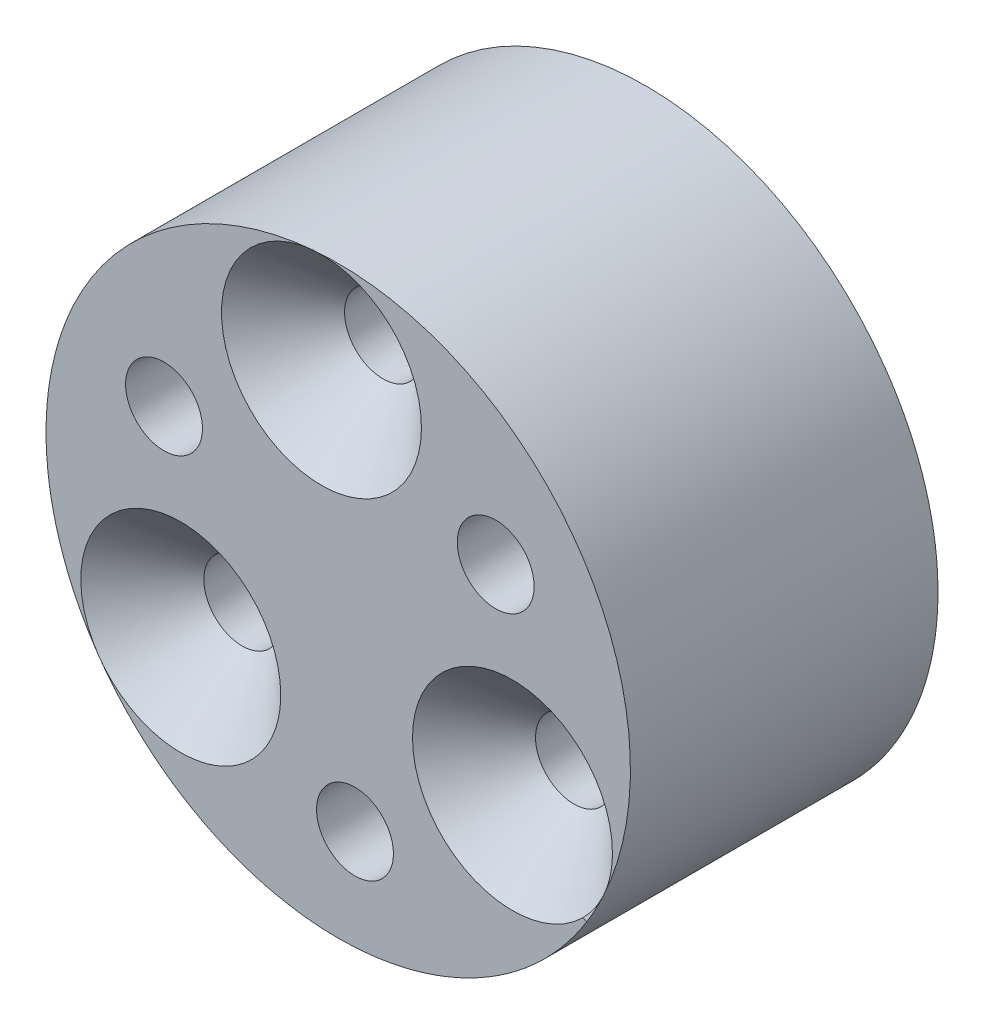
SolidWorks part; units mm, degrees
ref_plane "Top Plane" through (0, 0, 0) normal (0, 0, 1) x (1, 0, 0)
ref_plane "Right Plane" through (0, 0, 0) normal (0, 1, 0) x (1, 0, 0)
ref_plane "Front Plane" through (0, 0, 0) normal (1, 0, 0) x (0, 0, -1)
sketch "Sketch1" plane through (0, 0, 0) normal (0, 0, 1) x (1, 0, 0)
  line L0 (-0.5447, -33.7738) -> (0.5447, -46.2262) construction
  line L2 (5.1197, -36.4151) -> (-5.1197, -43.5849) construction
  line L4 (-5.6644, -37.3586) -> (5.6644, -42.6414) construction
  circle A0 centre (0, -40) radius 6.25 construction
  circle A1 centre (-0.5447, -33.7738) radius 1.25 construction
  circle A2 centre (0, -40) radius 9.5
  circle A3 centre (5.1197, -36.4151) radius 1.25
  circle A4 centre (0.5447, -46.2262) radius 1.25
  circle A5 centre (-5.6644, -37.3586) radius 1.25
  circle A6 centre (-5.1197, -43.5849) radius 1.25 construction
  circle A8 centre (-5.1197, -43.5849) radius 1.25
  circle A9 centre (-0.5447, -33.7738) radius 1.25
  circle A10 centre (5.6644, -42.6414) radius 1.25
  point P2 (5.6644, -42.6414)
  point P3 (-5.1197, -43.5849)
  point P5 (-0.5447, -33.7738)
  point P20 (0, 0)
  dimension "D1" = 19
  dimension "D3" = 2.5
  dimension "D2" = 60
extrude "Boss-Extrude1" add sketch "Sketch1" along normal blind 10
chamfer "Chamfer1" distance 2 angle 45 3 edges at (0.7053, -33.7738, 10) (-3.8697, -43.5849, 10) (6.9144, -42.6414, 10)
chamfer "Chamfer2" distance 2 angle 45 3 edges at (-4.4144, -37.3586, 0) (1.7947, -46.2262, 0) (6.3697, -36.4151, 0)
